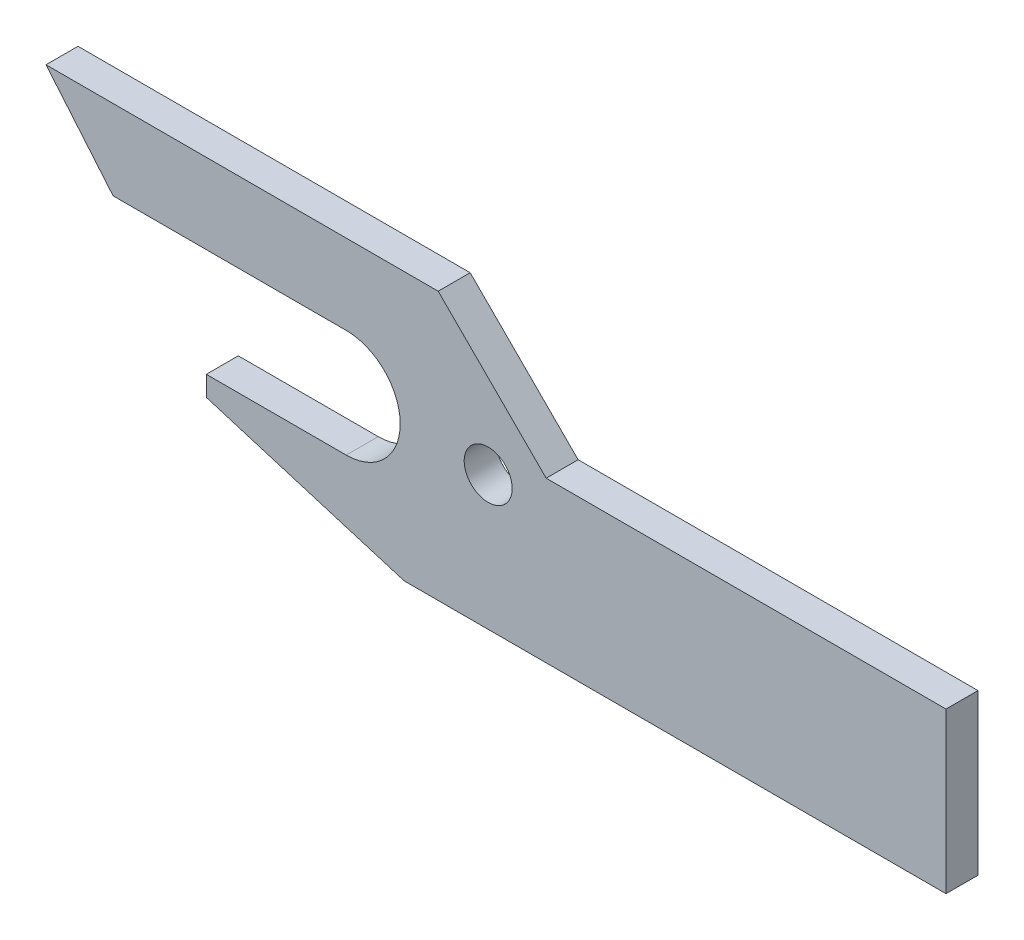
SolidWorks part; units mm, degrees
material "AISI 1020"
ref_plane "Спереди" through (0, 0, 0) normal (0, 0, 1) x (1, 0, 0)
ref_plane "Сверху" through (0, 0, 0) normal (0, 1, 0) x (1, 0, 0)
ref_plane "Справа" through (0, 0, 0) normal (1, 0, 0) x (0, 0, -1)
sketch "Эскиз1" plane through (0, 0, 0) normal (0, 0, 1) x (1, 0, 0)
  line L0 (-35, -13.5) -> (0, -13.5) construction
  line L1 (-35, -18.5) -> (-35, -13.5) construction
  line L2 (14.5, -33.5) -> (-35, -18.5) construction
  line L3 (150, -33.5) -> (14.5, -33.5) construction
  line L4 (150, 6.5) -> (150, -33.5) construction
  line L5 (50, 6.5) -> (150, 6.5) construction
  line L6 (23, 33.5) -> (50, 6.5) construction
  line L7 (-75.0906, 33.5) -> (23, 33.5) construction
  line L8 (-58.3086, 13.5) -> (-75.0906, 33.5) construction
  line L9 (0, 13.5) -> (-58.3086, 13.5) construction
  line L10 (-35, -13.5) -> (0, -13.5)
  line L11 (-35, -18.5) -> (-35, -13.5)
  line L12 (14.5, -33.5) -> (-35, -18.5)
  line L13 (150, -33.5) -> (14.5, -33.5)
  line L14 (150, 6.5) -> (150, -33.5)
  line L15 (50, 6.5) -> (150, 6.5)
  line L16 (23, 33.5) -> (50, 6.5)
  line L17 (-75.0906, 33.5) -> (23, 33.5)
  line L18 (-58.3086, 13.5) -> (-75.0906, 33.5)
  line L19 (0, 13.5) -> (-58.3086, 13.5)
  circle A0 centre (0, 0) radius 13.5 construction
  arc A1 (0, -13.5) -> (0, 13.5) centre (0, 0) ccw
  circle A2 centre (35.5, 0) radius 6 construction
  circle A3 centre (35.5, 0) radius 6
base flange "Базовая кромка1" sketch "Эскиз1" thickness 8 reverse thickness direction no parameters "D1"=0.74
sketch "Сгиб-Линии1" plane through (0, 0, 0) normal (0, 1, 0) x (1, 0, 0)
sketch "Граничная рамка1" plane through (0, 0, 0) normal (0, 1, 0) x (1, 0, 0)
sheet metal parameters "Листовой металл3" thickness 8 parameters "D1"=0.74
flat pattern "Развертка3" [suppressed]
sketch "Сгиб-Линии2" plane through (0, 0, 0) normal (0, 1, 0) x (1, 0, 0)
sketch "Граничная рамка2" [suppressed] plane through (0, 0, 0) normal (0, 1, 0) x (1, 0, 0)
